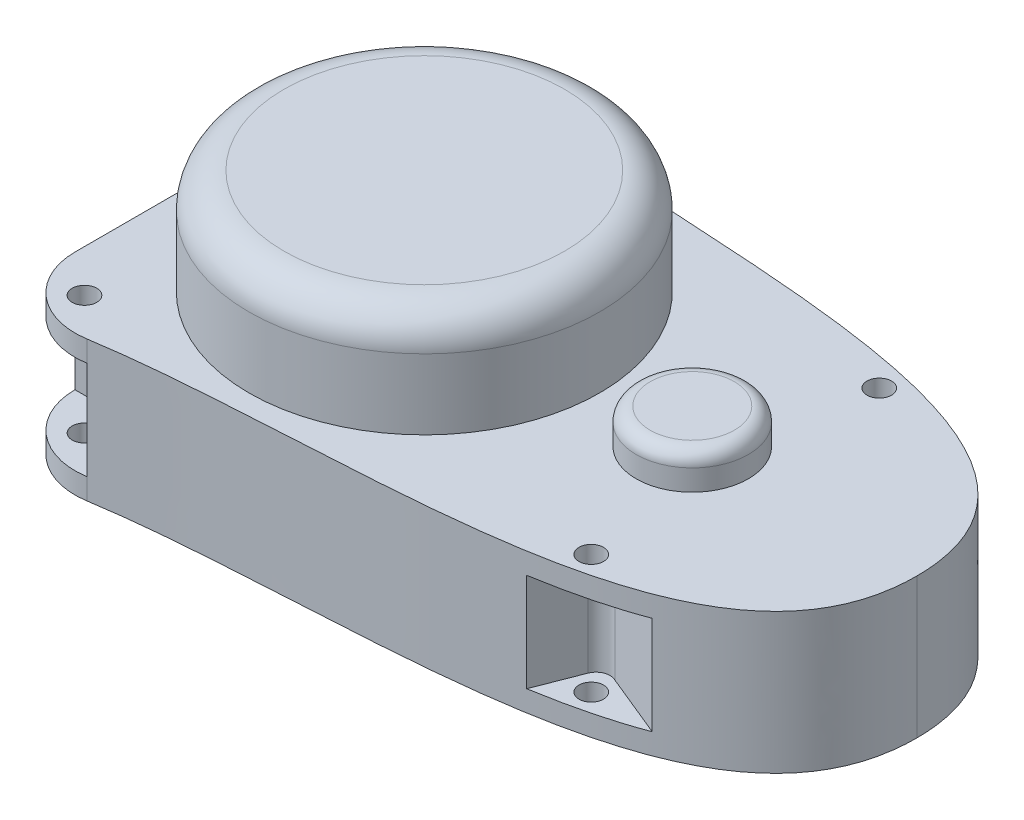
SolidWorks part; units mm, degrees
material "1060 Alloy"
ref_plane "Front Plane" through (0, 0, 0) normal (0, 0, 1) x (1, 0, 0)
ref_plane "Top Plane" through (0, 0, 0) normal (0, 1, 0) x (1, 0, 0)
ref_plane "Right Plane" through (0, 0, 0) normal (1, 0, 0) x (0, 0, -1)
sketch "Sketch2" plane through (0, 0, 0) normal (0, 1, 0) x (1, 0, 0)
  line L0 (-58, 20) -> (-58, -20)
  line L1 (-75.4951, 0) -> (96.6719, 0) construction
  arc A0 (-58, -20) -> (-45.9286, -29.7831) centre (-48, -20) ccw
  arc A1 (-58, 20) -> (-46.4313, 29.8762) centre (-48, 20) cw
  spline S0 degree 3 poles (-46.4313, 29.8762) (-13.9093, 24.7104) (42, 31.7309) (42, 0) knots 0 0 0 0 1 1 1 1
  spline S1 degree 3 poles (-46.4313, -29.8762) (-13.9093, -24.7104) (42, -31.7309) (42, 0) knots 0 0 0 0 1 1 1 1
  dimension "D2" = 10
  dimension "D3" = 58
  dimension "D1" = 40
  dimension "D4" = 42
  dimension "D5" = 36.1524
  dimension "D6" = 45.9286
  dimension "D7" = 46.4313
  dimension "D8" = 14.5765
extrude "Boss-Extrude2" add sketch "Sketch2" along normal blind 20 contours L1 L0 A0 S1 | L0 L1 S0 A1 region at (-12.7271, 0, -12.9432) region at (-12.7271, 0, 12.9432)
sketch "Sketch3" plane through (0, 0, 0) normal (0, 1, 0) x (1, 0, 0)
  line L0 (-58, 20) -> (-49.7074, 20)
  line L1 (-47.7322, 21.6863) -> (-46.4313, 29.8762)
  line L2 (-58, -20) -> (-49.7074, -20)
  line L3 (-47.7322, -21.6863) -> (-46.4313, -29.8762)
  line L4 (-49.7074, 22) -> (-55.7313, 29.0563) construction
  line L5 (-49.7074, -22) -> (-56.7632, -30.265) construction
  arc A0 (-58, -20) -> (-46.4313, -29.8762) centre (-48, -20) ccw construction
  arc A1 (-46.4313, 29.8762) -> (-58, 20) centre (-48, 20) ccw construction
  arc A2 (-58, -20) -> (-46.4313, -29.8762) centre (-48, -20) ccw
  arc A3 (-46.4313, 29.8762) -> (-58, 20) centre (-48, 20) ccw
  arc A4 (-49.7074, 20) -> (-47.7322, 21.6863) centre (-49.7074, 22) ccw
  arc A5 (-49.7074, -20) -> (-47.7322, -21.6863) centre (-49.7074, -22) cw
  circle A6 centre (-51.9799, 24.6619) radius 1.75
  circle A7 centre (-51.9799, -24.6619) radius 1.75
  point P16 (-48.4088, 20.4789)
  point P20 (-48.4088, -20.4789)
  point P22 (-54.4928, -27.6055)
  dimension "D1" = 2
  dimension "D2" = 3.5
  dimension "D4" = 3.5
  dimension "D3" = 5.5
  dimension "D5" = 5.5
extrude "Cut-Extrude1" cut sketch "Sketch3" along normal blind 14 from offset 3 contours A5 L2 A2 L3 A7 | L0 A4 L1 A3 A6 | A6 | A7 region at (-54.3935, 0, -27.4892) region at (-53.8537, 0, 20.1529) region at (-51.9799, 0, -24.6619) region at (-51.9799, 0, 24.6619)
extrude "Cut-Extrude2" cut sketch "Sketch3<3>" along normal blind 20 contours A7 | A6 region at (-51.9799, 0, -24.6619) region at (-51.9799, 0, 24.6619)
sketch "Sketch3<3>" plane through (0, 0, 0) normal (0, 1, 0) x (1, 0, 0) same geometry as "Sketch3"
sketch "Sketch4" plane through (0, 0, 0) normal (0, 1, 0) x (1, 0, 0)
  line L0 (11.1126, -24.7154) -> (13.5581, -18.4154)
  line L1 (16.3619, -17.3734) -> (25.3619, -21.0696)
  line L2 (-11, 0) -> (11, 0) construction
  line L3 (11.1126, 24.7154) -> (13.5581, 18.4154)
  line L4 (16.3619, 17.3734) -> (25.3619, 21.0696)
  line L5 (-75.4951, 0) -> (96.6719, 0) construction
  arc A0 (13.5581, -18.4154) -> (16.3619, -17.3734) centre (15.4226, -19.1391) cw
  arc A1 (13.5581, 18.4154) -> (16.3619, 17.3734) centre (15.4226, 19.1391) ccw
  circle A2 centre (16.1283, 20.5299) radius 1.75
  circle A4 centre (16.1283, -20.5299) radius 1.75
  spline S0 degree 3 poles (-46.4313, -29.8762) (-13.9093, -24.7104) (42, -31.7309) (42, 0) knots 0 0 0 0 1 1 1 1 construction
  spline S1 degree 3 poles (2401.1058, -1759.6528) (-2914.5709, 1714.4142) (2850.5639, -1808.6897) (-2335.8811, 1823.9647) knots -2.986866 -2.986866 -2.986866 -2.986866 3.538461 3.538461 3.538461 3.538461 only from (-46.4313, -29.8762) to (42, 0) construction
  spline S2 degree 3 poles (11.1126, -24.7154) (16.3043, -23.8439) (21.1351, -22.6807) (25.3619, -21.0696) knots 0.510512 0.510512 0.510512 0.510512 0.655796 0.655796 0.655796 0.655796
  spline S3 degree 3 poles (2401.1058, 1759.6528) (-2914.5709, -1714.4142) (2850.5639, 1808.6897) (-2335.8811, -1823.9647) knots -2.986866 -2.986866 -2.986866 -2.986866 3.538461 3.538461 3.538461 3.538461 only from (-46.4313, 29.8762) to (42, 0) construction
  spline S4 degree 3 poles (11.1126, 24.7154) (16.3043, 23.8439) (21.1351, 22.6807) (25.3619, 21.0696) knots 0.510512 0.510512 0.510512 0.510512 0.655796 0.655796 0.655796 0.655796
  dimension "D1" = 2
  dimension "D6" = 3.5
  dimension "D8" = 16.1283
  dimension "D2" = 6.3
  dimension "D3" = 21.0696
  dimension "D4" = 11.1126
  dimension "D5" = 13.5581
  dimension "D7" = 16.3619
  dimension "D9" = 20.5299
extrude "Cut-Extrude3" cut sketch "Sketch4" along normal blind 14 from offset 3 contours A4 | L0 S2 L1 A0 A4 | A2 | S4 L3 A1 L4 A2 region at (12.4858, 0, 21.6238) region at (18.2881, 0, -23.0812) region at (16.1283, 0, -20.5299) region at (16.1283, 0, 20.5299)
extrude "Cut-Extrude4" cut sketch "Sketch4<3>" along normal blind 20 contours A4 | A2 region at (16.1283, 0, -20.5299) region at (16.1283, 0, 20.5299)
sketch "Sketch4<3>" plane through (0, 0, 0) normal (0, 1, 0) x (1, 0, 0) same geometry as "Sketch4"
sketch "Sketch5" plane through (0, 20, 0) normal (0, 1, 0) x (1, 0, 0)
  line L0 (-75.4951, 0) -> (96.6719, 0) construction
  circle A0 centre (-28.2, 0) radius 25
  circle A1 centre (10, 0) radius 8
  dimension "D1" = 50
  dimension "D3" = 16
  dimension "D2" = 28.2
  dimension "D4" = 10
extrude "Boss-Extrude3" add sketch "Sketch5" along normal blind 15 contours A0 region at (-28.2, 20, 0)
extrude "Boss-Extrude4" add sketch "Sketch5<3>" along normal blind 5 contours A1 region at (10, 20, 0)
sketch "Sketch5<3>" plane through (0, 20, 0) normal (0, 1, 0) x (1, 0, 0) same geometry as "Sketch5"
fillet "Fillet1" radius 5 1 edges at (-28.2, 35, 25)
fillet "Fillet2" radius 2 1 edges at (10, 25, 8)
